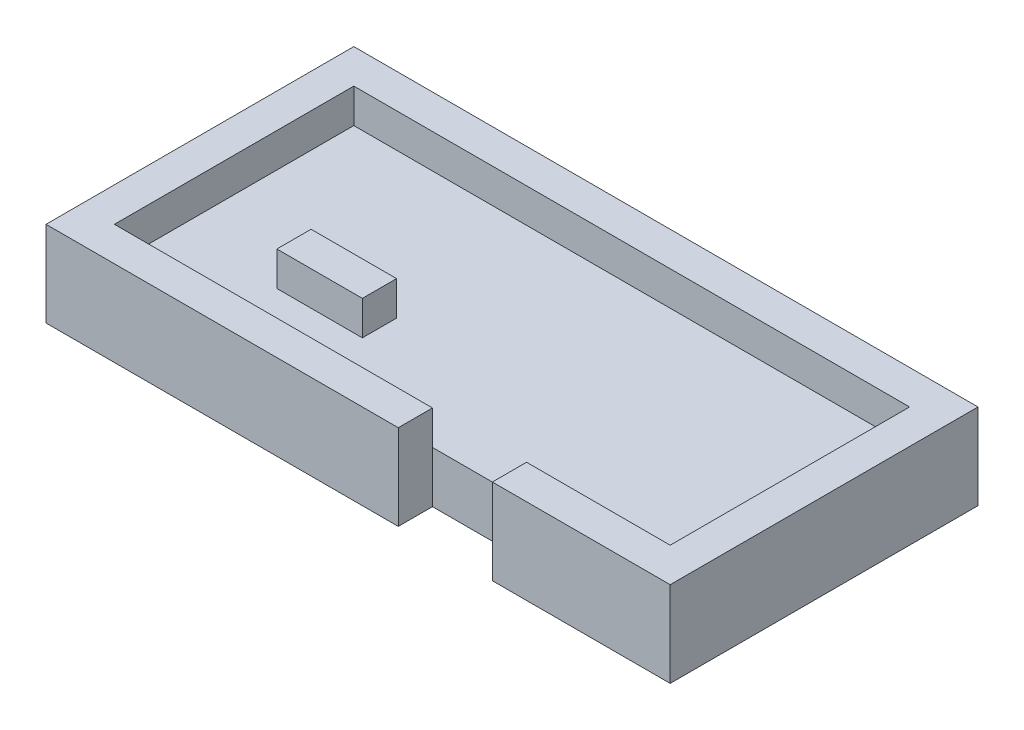
SolidWorks part; units mm, degrees
ref_plane "Front Plane" through (0, 0, 0) normal (0, 0, 1) x (1, 0, 0)
ref_plane "Top Plane" through (0, 0, 0) normal (0, 1, 0) x (1, 0, 0)
ref_plane "Right Plane" through (0, 0, 0) normal (1, 0, 0) x (0, 0, -1)
sketch "Sketch1" plane through (0, 0, 0) normal (0, 1, 0) x (1, 0, 0)
  line L1 (0, 0) -> (36.5, 0)
  line L2 (0, 0) -> (0, 18)
  line L3 (0, 18) -> (36.5, 18)
  line L4 (36.5, 0) -> (36.5, 18)
  dimension "D1" = 36.5
  dimension "D2" = 18
extrude "Boss-Extrude1" add sketch "Sketch1" against normal blind 5
sketch "Sketch2" plane through (0, 0, 0) normal (0, 1, 0) x (1, 0, 0)
  line L0 (36.5, 18) -> (0, 18) construction
  line L1 (2, 16) -> (34.5, 16)
  line L2 (2, 16) -> (2, 2)
  line L3 (2, 2) -> (34.5, 2)
  line L4 (34.5, 16) -> (34.5, 2)
  line L5 (0, 18) -> (0, 0) construction
  line L6 (0, 0) -> (36.5, 0) construction
  line L7 (36.5, 0) -> (36.5, 18) construction
  dimension "D1" = 2
  dimension "D2" = 2
  dimension "D3" = 2
  dimension "D4" = 2
extrude "Cut-Extrude1" cut sketch "Sketch2" against normal blind 2
sketch "Sketch3" plane through (0, -2, 0) normal (0, 1, 0) x (1, 0, 0)
  line L0 (34.5, 16) -> (2, 16) construction
  line L1 (8, 7.5) -> (13, 7.5)
  line L2 (8, 7.5) -> (8, 5.5)
  line L3 (8, 5.5) -> (13, 5.5)
  line L4 (13, 7.5) -> (13, 5.5)
  line L5 (2, 16) -> (2, 2) construction
  dimension "D1" = 2
  dimension "D2" = 8.5
  dimension "D3" = 5
  dimension "D4" = 6
extrude "Boss-Extrude2" add sketch "Sketch3" along normal blind 2
sketch "Sketch4" plane through (0, 0, -2) normal (0, 0, -1) x (-1, 0, 0)
  line L0 (-36.5, 0) -> (0, 0) construction
  line L1 (-26.1, 0) -> (-20.6, 0)
  line L2 (-26.1, 0) -> (-26.1, -5)
  line L3 (-26.1, -5) -> (-20.6, -5)
  line L4 (-20.6, 0) -> (-20.6, -5)
  line L5 (-36.5, -5) -> (-36.5, 0) construction
  dimension "D1" = 10.4
  dimension "D2" = 5.5
  dimension "D3" = 5
extrude "Cut-Extrude2" cut sketch "Sketch4" against normal up to next
